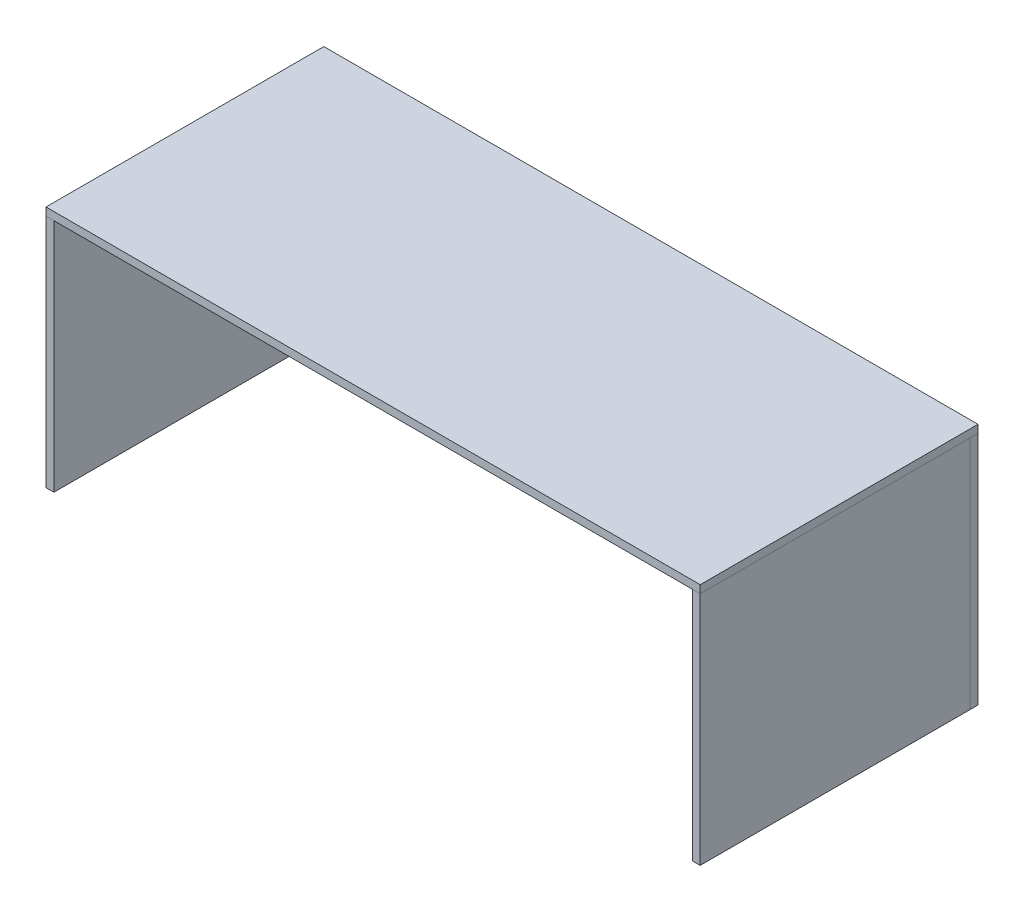
SolidWorks part; units mm, degrees
material "Acrylic (Medium-high impact)"
ref_plane "Front Plane" through (0, 0, 0) normal (0, 0, 1) x (1, 0, 0)
ref_plane "Top Plane" through (0, 0, 0) normal (0, 1, 0) x (1, 0, 0)
ref_plane "Right Plane" through (0, 0, 0) normal (1, 0, 0) x (0, 0, -1)
sketch "Sketch1" plane through (0, 0, 0) normal (0, 0, 1) x (1, 0, 0)
  line L1 (-231.775, 83.3437) -> (231.775, 83.3437)
  line L2 (-231.775, 83.3437) -> (-231.775, -83.3438)
  line L3 (-231.775, -83.3438) -> (231.775, -83.3438)
  line L4 (231.775, 83.3437) -> (231.775, -83.3438)
  line L5 (-231.775, 83.3437) -> (231.775, -83.3438) construction
  line L6 (-231.775, -83.3438) -> (231.775, 83.3437) construction
  point P0 (0, 0)
  dimension "D1" = 463.55
  dimension "D2" = 166.6875
extrude "Boss-Extrude1" add sketch "Sketch1" along normal blind 5.588
sketch "Sketch3" plane through (0, 83.3437, 0) normal (0, 1, 0) x (1, 0, 0)
  line L0 (231.775, 0) -> (-231.775, 0) construction
  line L1 (-231.775, -196.85) -> (231.775, -196.85)
  line L2 (-231.775, -196.85) -> (-231.775, 0)
  line L3 (-231.775, 0) -> (231.775, 0)
  line L4 (231.775, -196.85) -> (231.775, 0)
  line L5 (-231.775, -196.85) -> (231.775, 0) construction
  line L6 (-231.775, 0) -> (231.775, -196.85) construction
  point P0 (0, -98.425)
  dimension "D1" = 196.85
extrude "Boss-Extrude2" add sketch "Sketch3" along normal blind 5.588 separate body
sketch "Sketch5" plane through (231.775, 0, 0) normal (1, 0, 0) x (0, 0, -1)
  line L1 (-196.85, -83.3438) -> (-5.588, -83.3438)
  line L2 (-196.85, -83.3438) -> (-196.85, 83.3437)
  line L3 (-196.85, 83.3437) -> (-5.588, 83.3437)
  line L4 (-5.588, -83.3438) -> (-5.588, 83.3437)
  line L5 (-196.85, -83.3438) -> (-5.588, 83.3437) construction
  line L6 (-196.85, 83.3437) -> (-5.588, -83.3438) construction
  line L7 (-196.85, 88.9317) -> (-196.85, 83.3437) construction
  line L8 (-196.85, 83.3437) -> (0, 83.3437) construction
  line L9 (-5.588, -83.3438) -> (0, -83.3438) construction
  point P0 (-101.219, 0)
extrude "Boss-Extrude3" add sketch "Sketch5" against normal blind 5.588 separate body
sketch "Sketch6" plane through (-231.775, 0, 0) normal (-1, 0, 0) x (0, 0, 1)
  line L0 (196.85, -83.3437) -> (5.588, -83.3437) construction
  line L1 (196.85, -83.3437) -> (5.588, -83.3437)
  line L2 (196.85, -83.3437) -> (196.85, 83.3438)
  line L3 (196.85, 83.3438) -> (5.588, 83.3438)
  line L4 (5.588, -83.3437) -> (5.588, 83.3438)
  line L5 (196.85, -83.3437) -> (5.588, 83.3438) construction
  line L6 (196.85, 83.3438) -> (5.588, -83.3437) construction
  point P0 (101.219, 0)
extrude "Boss-Extrude4" [suppressed] add sketch "Sketch6" against normal blind 4.7625 separate body
sketch "Sketch7" [suppressed] plane through (0, 0, 4.7625) normal (0, 0, -1) x (-1, 0, 0)
  line L1 (-242.0938, -101.854) -> (-235.7438, -101.854)
  line L2 (-242.0938, -101.854) -> (-242.0938, -95.504)
  line L3 (-242.0938, -95.504) -> (-235.7438, -95.504)
  line L4 (-235.7438, -101.854) -> (-235.7438, -95.504)
  line L6 (-236.5375, -101.6) -> (-241.3, -101.6) construction
  line L7 (-238.9188, -101.854) -> (-238.9188, -101.6) construction
  line L8 (0, 0) -> (0, -111.4304) construction
  line L9 (238.9188, -101.854) -> (238.9188, -101.6) construction
  line L10 (235.7438, -101.854) -> (235.7438, -95.504)
  line L11 (242.0938, -95.504) -> (235.7438, -95.504)
  line L12 (242.0938, -101.854) -> (242.0938, -95.504)
  line L13 (242.0938, -101.854) -> (235.7438, -101.854)
  dimension "D1" = 0.254
  dimension "D2" = 6.35
  dimension "D3" = 6.35
extrude "Boss-Extrude5" [suppressed] add sketch "Sketch7" against normal up to surface (160.3375 mm away) up to face at (228.981, 0, 196.85)
sketch "Sketch8" plane through (-231.775, 0, 0) normal (-1, 0, 0) x (0, 0, 1)
  line L1 (5.588, -83.3437) -> (196.85, -83.3437)
  line L2 (5.588, -83.3437) -> (5.588, 83.3437)
  line L3 (5.588, 83.3437) -> (196.85, 83.3437)
  line L4 (196.85, -83.3437) -> (196.85, 83.3437)
extrude "Boss-Extrude6" add sketch "Sketch8" against normal blind 5.588 separate body
